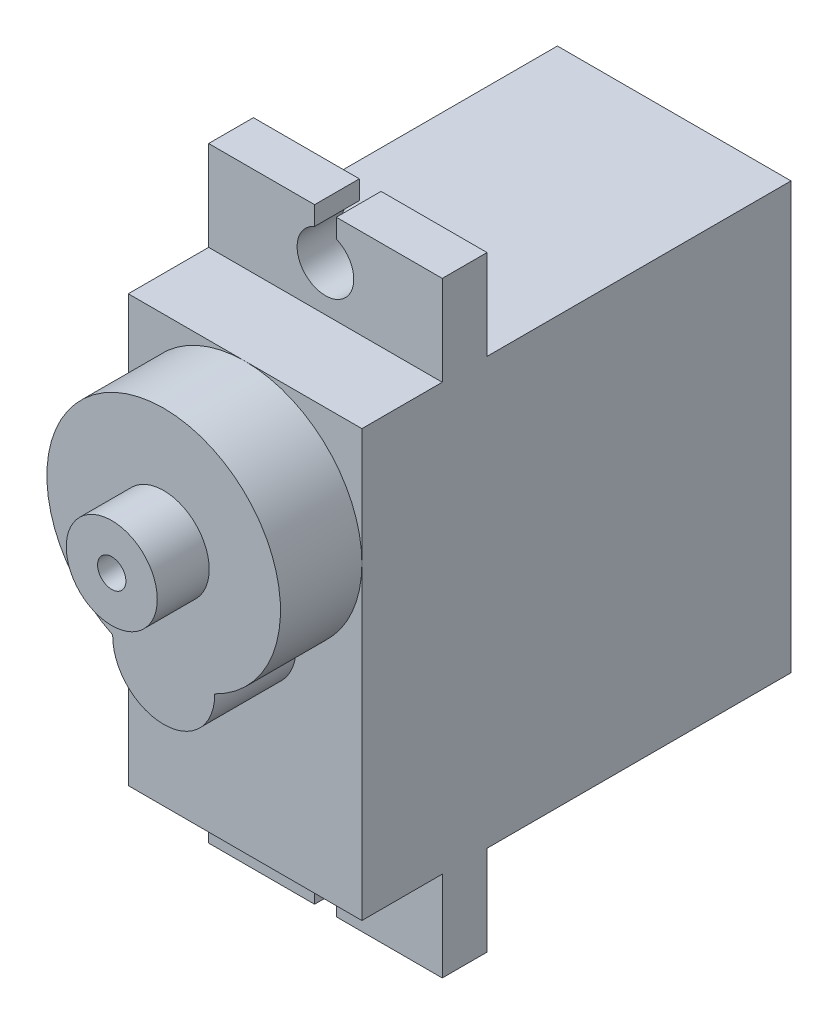
SolidWorks part; units mm, degrees
ref_plane "Front Plane" through (0, 0, 0) normal (0, 0, 1) x (1, 0, 0)
ref_plane "Top Plane" through (0, 0, 0) normal (0, 1, 0) x (1, 0, 0)
ref_plane "Right Plane" through (0, 0, 0) normal (1, 0, 0) x (0, 0, -1)
sketch "Sketch1" plane through (0, 0, 0) normal (0, 0, 1) x (1, 0, 0)
  line L1 (-6.1849, -11.2776) -> (6.1849, -11.2776)
  line L2 (-6.1849, -11.2776) -> (-6.1849, 11.2776)
  line L3 (-6.1849, 11.2776) -> (6.1849, 11.2776)
  line L4 (6.1849, -11.2776) -> (6.1849, 11.2776)
  line L5 (-6.1849, -11.2776) -> (6.1849, 11.2776) construction
  line L6 (-6.1849, 11.2776) -> (6.1849, -11.2776) construction
  point P0 (0, 0)
  dimension "D1" = 12.3698
  dimension "D2" = 22.5552
extrude "Boss-Extrude1" add sketch "Sketch1" along normal mid plane 22.7203
ref_plane "Plane1" through (0, 0, 7.1056) normal (0, 0, 1) x (1, 0, 0)
sketch "Sketch2" plane through (0, 0, 7.1056) normal (0, 0, 1) x (1, 0, 0)
  line L0 (-0.575, 16.0401) -> (-6.1849, 16.0401)
  line L1 (-6.1849, 16.0401) -> (-6.1849, 11.2776)
  line L2 (-6.1849, 11.2776) -> (6.1849, 11.2776)
  line L3 (6.1849, 11.2776) -> (6.1849, 16.0401)
  line L4 (6.1849, 16.0401) -> (0.575, 16.0401)
  line L5 (0.575, 16.0401) -> (0.575, 15.0401)
  line L6 (-0.575, 15.0401) -> (-0.575, 16.0401)
  line L7 (-1.5, 13.6547) -> (1.5, 13.6547) construction
  arc A0 (0.575, 15.0401) -> (-0.575, 15.0401) centre (0, 13.6547) cw
  dimension "D2" = 3
  dimension "D1" = 4.7625
  dimension "D3" = 1
  dimension "D4" = 1.15
extrude "Boss-Extrude2" add sketch "Sketch2" against normal blind 2.37
mirror "Mirror1" about plane through (0, 0, 0) normal (0, 1, 0) of "Boss-Extrude2"
sketch "Sketch3" plane through (0, 0, 11.3601) normal (0, 0, 1) x (1, 0, 0)
  line L0 (6.1849, 11.2776) -> (-6.1849, 11.2776) construction
  line L1 (6.1849, -11.2776) -> (6.1849, 11.2776) construction
  line L2 (2.7, -0.5224) -> (2.7, -0.4717)
  line L3 (-2.7, -0.5224) -> (-2.7, -0.4717)
  line L4 (0, 11.2776) -> (0, -3.2224) construction
  arc A0 (2.7, -0.4717) -> (-2.7, -0.4717) centre (0, 5.0927) ccw
  arc A1 (2.7, -0.5224) -> (-2.7, -0.5224) centre (0, -0.5224) cw
  dimension "D1" = 5.4
  dimension "D2" = 14.5
extrude "Boss-Extrude3" add sketch "Sketch3" along normal blind 4.31
sketch "Sketch4" plane through (0, 0, 15.6702) normal (0, 0, 1) x (1, 0, 0)
  circle A0 centre (0, 5.0927) radius 2.41
  circle A1 centre (0, 5.0927) radius 0.75
  dimension "D1" = 4.82
  dimension "D2" = 1.5
extrude "Boss-Extrude4" add sketch "Sketch4" along normal blind 2.75
ref_axis "Axis1" through (0, 5.0927, 22.3459) along (0, 0, -1)
ref_axis "Axis2" through (0, 13.6547, 4.7356) along (0, 0, 1)
ref_axis "Axis3" through (0, -13.6547, 4.7356) along (0, 0, 1)
